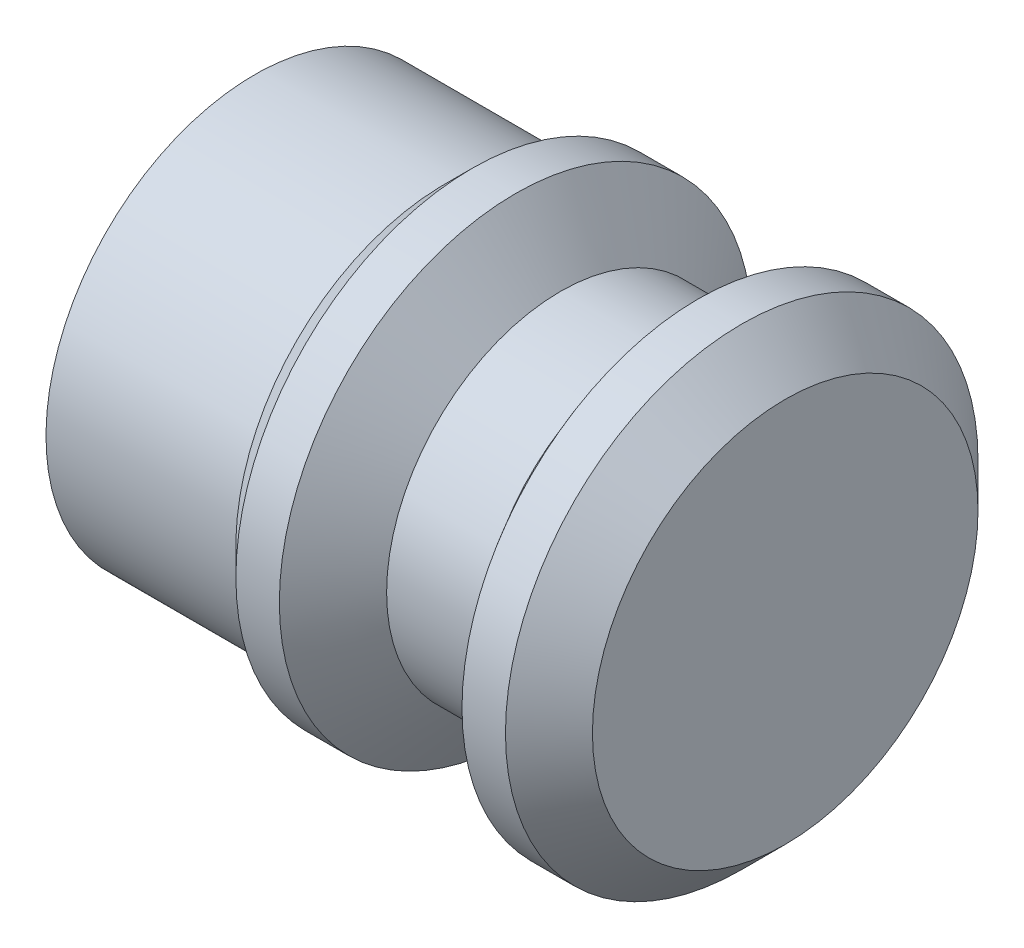
SolidWorks part; units mm, degrees
ref_plane "Front Plane" through (0, 0, 0) normal (0, 0, 1) x (1, 0, 0)
ref_plane "Top Plane" through (0, 0, 0) normal (0, 1, 0) x (1, 0, 0)
ref_plane "Right Plane" through (0, 0, 0) normal (1, 0, 0) x (0, 0, -1)
sketch "Sketch1" plane through (0, 0, 0) normal (0, 1, 0) x (1, 0, 0)
  line L0 (-23.013, 0) -> (32.9424, 0)
  line L1 (-6.15, 0) -> (0, 0)
  line L2 (0, 0) -> (0, 4.075)
  line L3 (0, 4.075) -> (-1.5, 4.075)
  line L4 (-1.5, 4.075) -> (-2.275, 3)
  line L5 (-2.275, 3) -> (-3.875, 3)
  line L6 (-3.875, 3) -> (-4.65, 4.075)
  line L7 (-4.65, 4.075) -> (-6.15, 4.075)
  line L8 (-6.15, 4.075) -> (-6.15, 0)
  line L10 (-4.65, 4.075) -> (-4.6458, 4.07)
  line L11 (-3.075, 3) -> (-3.075, 4.075)
  dimension "D1" = 6.15
  dimension "D2" = 4.075
  dimension "D3" = 0
  dimension "D4" = 3
  dimension "D5" = 0
  dimension "D6" = 1.5
  dimension "D7" = 1.5
  dimension "D8" = 1.6
  dimension "D10" = 0
revolve "Revolve1" add sketch "Sketch1" angle 360 about L0 region at (-3.075, 0, -1.8607)
chamfer "Chamfer1" distance 0.75 angle 45 2 edges at (0, 0, 4.075) (-6.15, 0, 4.075)
sketch "Sketch2" plane through (-6.15, 0, 0) normal (-1, 0, 0) x (0, 0, 1)
  circle A0 centre (0, 0) radius 3.6
  dimension "D1" = 7.2
extrude "Boss-Extrude1" add sketch "Sketch2" along normal blind 3 and the other way blind 1
sketch "Sketch3" plane through (-9.15, 0, 0) normal (-1, 0, 0) x (0, 0, 1)
  circle A0 centre (0, 0) radius 0.55
  dimension "D1" = 1.1
extrude "Boss-Extrude2" add sketch "Sketch3" along normal blind 2
sketch "Sketch4" plane through (-9.15, 0, 0) normal (-1, 0, 0) x (0, 0, 1)
  line L0 (0, 0) -> (0, -3.6)
  line L1 (0, 0) -> (-3.2277, -1.5944)
  circle A0 centre (0, 0) radius 2.05
  circle A1 centre (0, 0) radius 3.6
  circle M1 centre (0, 0) radius 3.6
  dimension "D1" = 4.1
  dimension "D2" = 7.2
  dimension "D3" = 3.8
extrude "Cut-Extrude1" cut sketch "Sketch4" against normal blind 2.5 contours A0 L1 L0 M1 region at (-9.15, -2.3349, -1.4508)
